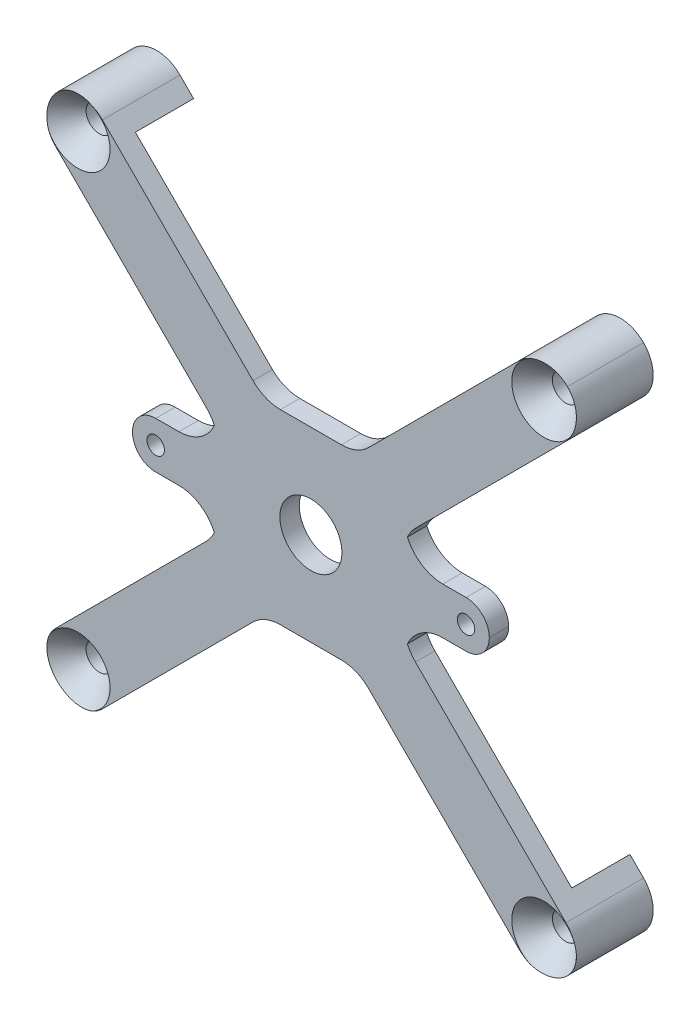
SolidWorks part; units mm, degrees
ref_plane "Front Plane" through (0, 0, 0) normal (0, 0, 1) x (1, 0, 0)
ref_plane "Top Plane" through (0, 0, 0) normal (0, 1, 0) x (1, 0, 0)
ref_plane "Right Plane" through (0, 0, 0) normal (1, 0, 0) x (0, 0, -1)
sketch "Sketch1" plane through (0, 0, 0) normal (0, 0, 1) x (1, 0, 0)
  line L0 (0, 0) -> (-7.477, 7.477) construction
  line L1 (0, 0) -> (0, -24.8803) construction
  line L2 (11.8659, 11.8659) -> (26.2689, 26.2689) construction
  circle A0 centre (0, 0) radius 42.5
  point P9 (-30.052, 30.052)
  point P10 (30.052, 30.052)
  point P11 (30.052, -30.052)
  point P12 (-30.052, -30.052)
  point P13 (-20, 0)
  point P14 (20, 0)
  point P15 (0, 0)
  point P16 (0, 0)
  dimension "D1" = 85
  dimension "D2" = 45
  dimension "D3" = 45
  dimension "D4" = 20
  dimension "D5" = 20
sketch "Sketch2" plane through (0, 0, 0) normal (0, 0, 1) x (1, 0, 0)
  line L0 (-6, 12.0104) -> (-29.8753, 35.8857)
  line L1 (-29.8753, 35.8857) -> (-35.8857, 29.8753)
  line L2 (-35.8857, 29.8753) -> (-12.0104, 6)
  line L3 (-6, 12.0104) -> (6, 12.0104)
  line L4 (6, 12.0104) -> (29.8753, 35.8857)
  line L5 (29.8753, 35.8857) -> (35.8857, 29.8753)
  line L6 (35.8857, 29.8753) -> (12.0104, 6)
  line L7 (12.0104, 6) -> (12.0104, -6)
  line L8 (12.0104, -6) -> (35.8857, -29.8753)
  line L9 (35.8857, -29.8753) -> (29.8753, -35.8857)
  line L10 (29.8753, -35.8857) -> (6, -12.0104)
  line L11 (6, -12.0104) -> (-6, -12.0104)
  line L12 (-6, -12.0104) -> (-29.8753, -35.8857)
  line L13 (-29.8753, -35.8857) -> (-35.8857, -29.8753)
  line L14 (-35.8857, -29.8753) -> (-12.0104, -6)
  line L15 (-12.0104, -6) -> (-12.0104, 6)
  line L16 (141421.3562, -141421.3562) -> (-141428.8332, 141428.8332) construction
  line L17 (-141409.4904, -141409.4904) -> (141447.6251, 141447.6251) construction
  circle A0 centre (0, 0) radius 49 construction
  point P19 (32.8805, -32.8805)
  point P22 (32.8805, 32.8805)
  point P25 (-32.8805, 32.8805)
  point P26 (-32.8805, -32.8805)
  point P32 (0, 0)
  dimension "D1" = 98
  dimension "D2" = 8.5
  dimension "D3" = 8.5
  dimension "D4" = 8.5
  dimension "D5" = 8.5
  dimension "D6" = 4
  dimension "D7" = 4
  dimension "D8" = 4
  dimension "D9" = 4
  dimension "D11" = 12
  dimension "D12" = 12
  dimension "D13" = 12
  dimension "D14" = 12
extrude "Boss-Extrude1" add sketch "Sketch2" along normal blind 10
sketch "Sketch3" plane through (0, 0, 0) normal (0, 0, 1) x (1, 0, 0)
  line L0 (0, 200000) -> (0, -200024.8803) construction
  line L1 (-23, 3) -> (23, 3)
  line L2 (-23, 3) -> (-23, -3)
  line L3 (-23, -3) -> (23, -3)
  line L4 (23, 3) -> (23, -3)
  point P4 (-23, 0)
  point P5 (0, 3)
  dimension "D1" = 6
  dimension "D2" = 3
extrude "Boss-Extrude2" add sketch "Sketch3" along normal up to surface (10 mm away) up to face at (0, 0, 10)
hole_wizard "CSK for #4 Oval Head Machine Screw1" positions "Sketch5" profile "Sketch6" countersink size "#4" standard "ANSI Inch"
sketch "Sketch5" plane through (0, 0, 10) normal (0, 0, 1) x (1, 0, 0)
  point P0 (-30.052, 30.052)
  point P3 (30.052, 30.052)
  point P6 (30.052, -30.052)
  point P9 (-30.052, -30.052)
sketch "Sketch6" plane through (-30.052, 30.052, 10) normal (1, 0, 0) x (0, -1, 0)
  line L0 (0, 0) -> (0, 26.0378)
  line L1 (0, 26.0378) -> (1.7272, 25)
  line L2 (1.7272, 25) -> (1.7272, 2.8003)
  line L3 (1.7272, 2.8003) -> (4.1614, 0)
  line L5 (4.1614, 0) -> (0, 0)
  line L6 (-1.7272, 2.8003) -> (-4.1614, 0) construction
  line L10 (0, 26.0378) -> (-1.7272, 25) construction
  line L11 (0, -6.35) -> (0, 107.95) construction
  dimension "Hole Dia." = 3.4544
  dimension "Hole Depth" = 25
  dimension "Near C'Sink Dia." = 8.3228
  dimension "Near C'Sink Angle" = 82
  dimension "Drill Angle" = 118
sketch "Sketch7" plane through (0, 0, 10) normal (0, 0, 1) x (1, 0, 0)
  circle A0 centre (20, 0) radius 1.125
  circle A1 centre (-20, 0) radius 1.125
  dimension "D1" = 2.25
  dimension "D2" = 2.25
extrude "Cut-Extrude1" cut sketch "Sketch7" against normal through all
sketch "Sketch8" plane through (0, 0, 10) normal (0, 0, 1) x (1, 0, 0)
  circle A0 centre (0, 0) radius 4
  dimension "D1" = 8
extrude "Cut-Extrude2" cut sketch "Sketch8" against normal through all
fillet "Fillet1" radius 4.25 8 edges at (35.8857, -29.8753, 5) (29.8753, -35.8857, 5) (29.8753, 35.8857, 5) (35.8857, 29.8753, 5) (-29.8753, 35.8857, 5) (-35.8857, 29.8753, 5) (-35.8857, -29.8753, 5) (-29.8753, -35.8857, 5)
fillet "Fillet2" radius 3 4 edges at (23, 3, 5) (23, -3, 5) (-23, 3, 5) (-23, -3, 5)
fillet "Fillet3" radius 5 12 edges at (-6, 12.0104, 5) (6, 12.0104, 5) (-12.0104, 3, 5) (-12.0104, 6, 5) (-12.0104, -6, 5) (-12.0104, -3, 5) (-6, -12.0104, 5) (6, -12.0104, 5) (12.0104, -3, 5) (12.0104, -6, 5) (12.0104, 3, 5) (12.0104, 6, 5)
sketch "Sketch9" plane through (0, 0, 0) normal (0, 0, -1) x (-1, 0, 0)
  circle A0 centre (0, 0) radius 40
  dimension "D1" = 80
extrude "Cut-Extrude3" cut sketch "Sketch9" against normal offset from surface (7.5 mm away) 2.5 up to face at (4, 0, 10)
